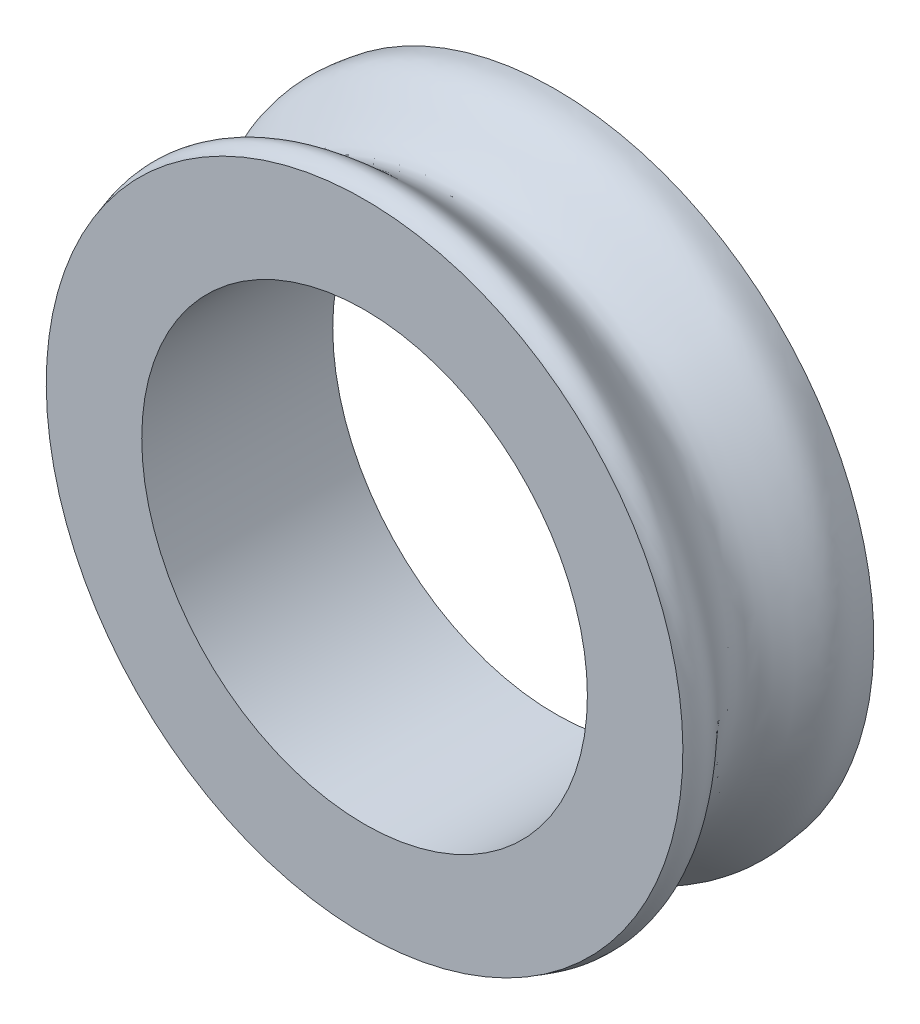
SolidWorks part; units mm, degrees
ref_plane "Front Plane" through (0, 0, 0) normal (0, 0, 1) x (1, 0, 0)
ref_plane "Top Plane" through (0, 0, 0) normal (0, 1, 0) x (1, 0, 0)
ref_plane "Right Plane" through (0, 0, 0) normal (1, 0, 0) x (0, 0, -1)
sketch "Sketch1" plane through (0, 0, 0) normal (0, 0, 1) x (1, 0, 0)
  circle A0 centre (0, 0) radius 50
  dimension "D1" = 100
ref_plane "Plane1" through (0, 0, -5) normal (0, 0, 1) x (1, 0, 0)
ref_plane "Plane2" through (0, 0, -25) normal (0, 0, 1) x (1, 0, 0)
ref_plane "Plane3" through (0, 0, -30) normal (0, 0, 1) x (1, 0, 0)
ref_plane "Plane4" through (0, 0, -15) normal (0, 0, 1) x (1, 0, 0)
sketch "Sketch3" plane through (0, 0, -5) normal (0, 0, 1) x (1, 0, 0)
  circle A0 centre (0, 0) radius 50 construction
  circle A1 centre (0, 0) radius 50
sketch "Sketch4" plane through (0, 0, -15) normal (0, 0, 1) x (1, 0, 0)
  circle A0 centre (0, 0) radius 43.5
  dimension "D1" = 87
sketch "Sketch5" plane through (0, 0, -25) normal (0, 0, 1) x (1, 0, 0)
  circle A0 centre (0, 0) radius 50 construction
  circle A1 centre (0, 0) radius 50
sketch "Sketch6" plane through (0, 0, -30) normal (0, 0, 1) x (1, 0, 0)
  circle A0 centre (0, 0) radius 50 construction
  circle A1 centre (0, 0) radius 50
loft "Loft1" add profiles "Sketch1", "Sketch3", "Sketch4", "Sketch5", "Sketch6" connector at (-48.8231, -10.7845, 0) connector at (-49.9938, 0.7854, -5) connector at (-43.1904, -5.1807, -15) connector at (-48.5139, -12.0995, -25) connector at (-47.4647, -15.7195, -30)
sketch "Sketch7" plane through (0, 0, -30) normal (0, 0, -1) x (-1, 0, 0)
  circle A0 centre (0, 0) radius 35
  dimension "D1" = 70
extrude "Cut-Extrude1" cut sketch "Sketch7" against normal through all
